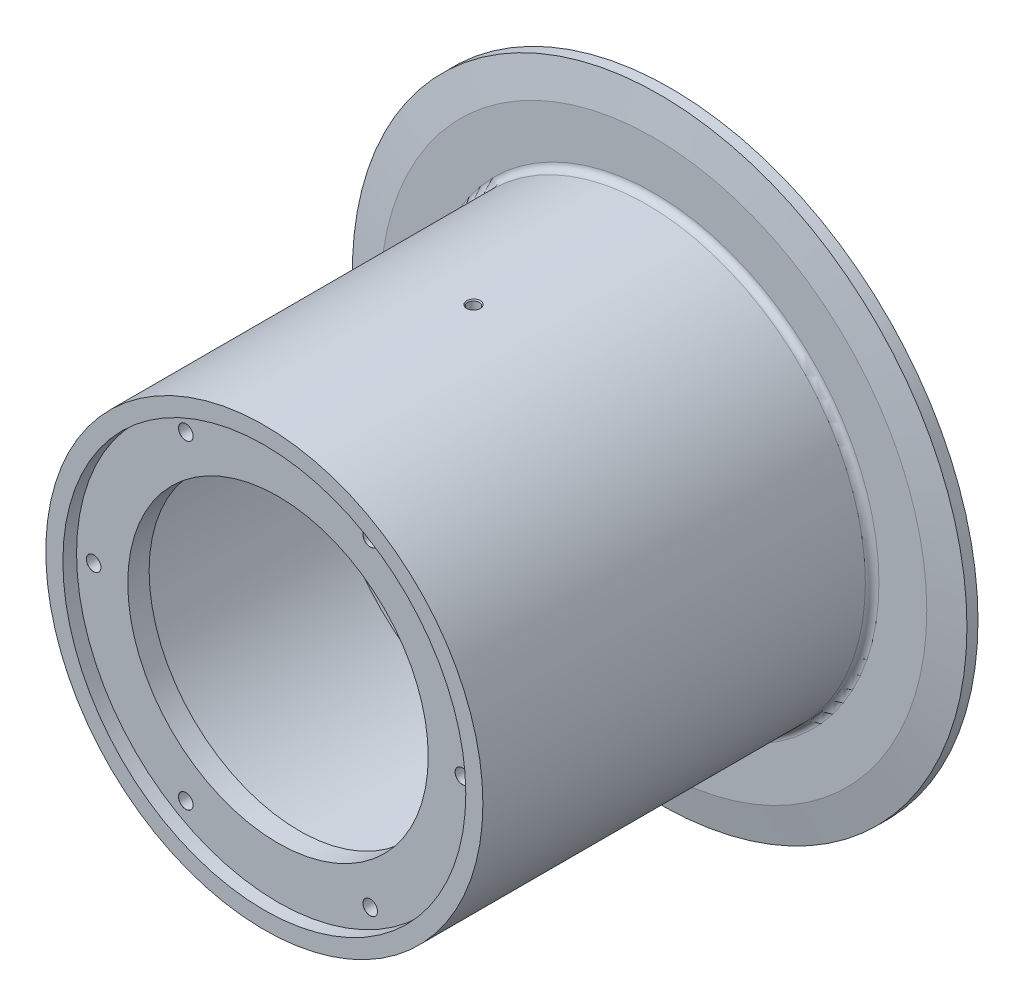
SolidWorks part; units mm, degrees
ref_plane "前视基准面" through (0, 0, 0) normal (0, 0, 1) x (1, 0, 0)
ref_plane "上视基准面" through (0, 0, 0) normal (0, 1, 0) x (1, 0, 0)
ref_plane "右视基准面" through (0, 0, 0) normal (1, 0, 0) x (0, 0, -1)
sketch "草图1" plane through (0, 0, 0) normal (0, 0, 1) x (1, 0, 0)
  circle A0 centre (0, 0) radius 180
  dimension "D1" = 360
extrude "凸台-拉伸1" add sketch "草图1" along normal blind 10
sketch "草图2" plane through (0, 0, 0) normal (0, 0, 1) x (1, 0, 0)
  circle A0 centre (0, 0) radius 128
  dimension "D1" = 256
extrude "凸台-拉伸2" add sketch "草图2" along normal blind 238
sketch "草图3" plane through (0, 0, 0) normal (0, 0, -1) x (-1, 0, 0)
  circle A0 centre (0, 0) radius 120
  dimension "D1" = 240
extrude "切除-拉伸1" cut sketch "草图3" against normal blind 86
sketch "草图4" plane through (0, 0, 86) normal (0, 0, -1) x (-1, 0, 0)
  circle A0 centre (0, 0) radius 118
  dimension "D1" = 236
extrude "切除-拉伸2" cut sketch "草图4" against normal blind 131.5
sketch "草图5" plane through (0, 0, 217.5) normal (0, 0, -1) x (-1, 0, 0)
  circle A0 centre (0, 0) radius 88
  dimension "D1" = 176
extrude "切除-拉伸3" cut sketch "草图5" against normal through all
sketch "草图6" plane through (0, 0, 238) normal (0, 0, 1) x (1, 0, 0)
  circle A0 centre (0, 0) radius 118
  dimension "D1" = 236
extrude "切除-拉伸4" cut sketch "草图6" against normal blind 8
sketch "草图7" plane through (0, 0, 230) normal (0, 0, 1) x (1, 0, 0)
  line L0 (130.9, 0) -> (-130.9, 0) construction
  circle A0 centre (0, 0) radius 108 construction
  point P0 (108, 0)
  point P6 (54, -93.5307)
  point P9 (-54, -93.5307)
  point P10 (-108, 0)
  point P11 (-54, 93.5307)
  point P12 (54, 93.5307)
  dimension "D1" = 216
  dimension "D2" = 6
hole_wizard "M10 螺纹孔的螺纹孔钻头1" positions "草图7" profile "草图8" hole size "M10" standard "GB" end condition up to next
sketch "草图8" plane through (108, 0, 230) normal (1, 0, 0) x (0, -1, 0)
  line L0 (0, 0) -> (0, 12.5)
  line L1 (0, 12.5) -> (4.25, 12.5)
  line L2 (4.25, 12.5) -> (4.25, 0.025)
  line L3 (4.25, 0.025) -> (4.275, 0)
  line L5 (4.275, 0) -> (0, 0)
  line L6 (-4.25, 0.025) -> (-4.275, 0) construction
  line L11 (0, -6.35) -> (0, 107.95) construction
  dimension "通孔孔直径" = 8.5
  dimension "通孔孔深度" = 12.5
  dimension "近端锥形沉头孔直径" = 8.55
  dimension "近端锥形沉头孔角度" = 90
fillet "圆角1" radius 4 1 edges at (128, 0, 10)
chamfer "倒角1" distance 20 angle 10 1 edges at (180, 0, 10) first distance on face at (132, 0, 10)
hole_wizard "M8 螺纹孔1" positions "3D草图1" profile "草图9" tap size "M8" standard "GB" end condition up to next
sketch3d "3D草图1"
  point P0 (0, 128, 115.5)
  dimension "D1" = 115.5
sketch "草图9" plane through (0, 128, 115.5) normal (1, 0, 0) x (0, 0, 1)
  line L0 (0, 0) -> (0, 10)
  line L1 (0, 10) -> (3.4, 10)
  line L2 (3.4, 10) -> (3.4, 0.625)
  line L3 (3.4, 0.625) -> (4.025, 0)
  line L5 (4.025, 0) -> (0, 0)
  line L6 (-3.4, 0.625) -> (-4.025, 0) construction
  line L11 (0, -6.35) -> (0, 107.95) construction
  dimension "通孔螺纹孔钻头直径" = 6.8
  dimension "通孔螺纹孔钻头深度" = 10
  dimension "近端锥形沉头孔直径" = 8.05
  dimension "近端锥形沉头孔角度" = 90
cosmetic thread "孔螺纹线1" parameters "D2"=8
